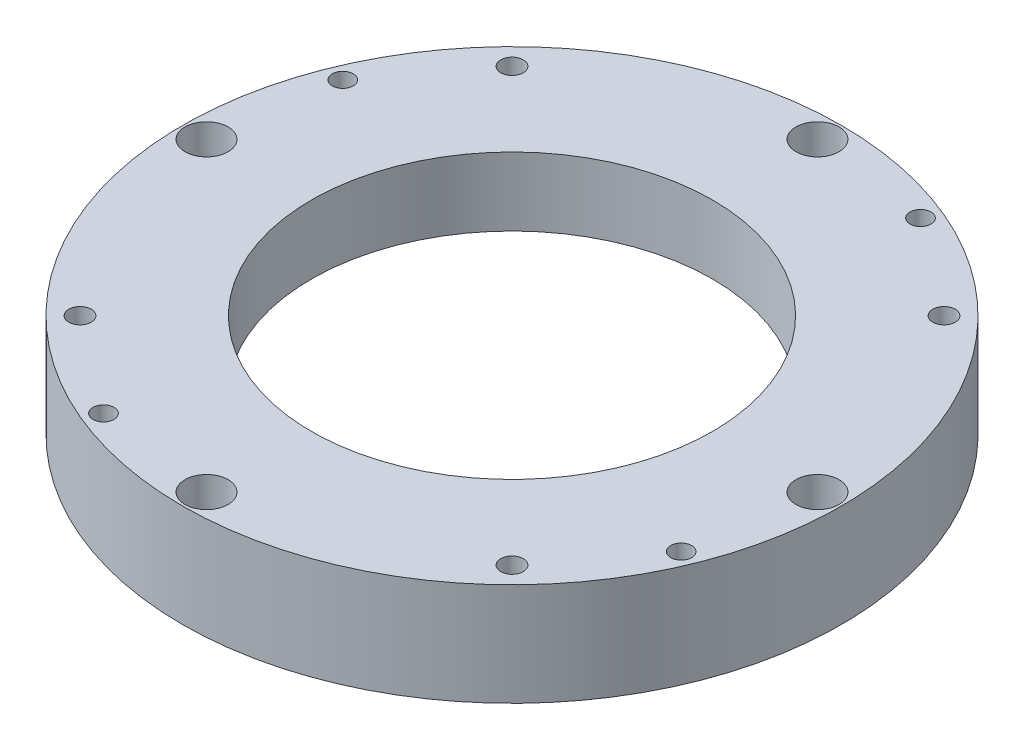
SolidWorks part; units mm, degrees
ref_plane "Front Plane" through (0, 0, 0) normal (0, 0, 1) x (1, 0, 0)
ref_plane "Top Plane" through (0, 0, 0) normal (0, 1, 0) x (1, 0, 0)
ref_plane "Right Plane" through (0, 0, 0) normal (1, 0, 0) x (0, 0, -1)
sketch "Sketch1" plane through (0, 0, 0) normal (0, 1, 0) x (1, 0, 0)
  line L0 (0, 0) -> (42.5, 0) construction
  circle A0 centre (0, 0) radius 45.85
  circle A1 centre (0, 0) radius 27.9
  circle A2 centre (42.5, 0) radius 1.5635
  circle A3 centre (30.052, -30.052) radius 1.5635
  circle A4 centre (0, -42.5) radius 1.5635
  circle A5 centre (0, 0) radius 39.5
  circle A6 centre (-30.052, -30.052) radius 1.5635
  circle A7 centre (-42.5, 0) radius 1.5635
  circle A8 centre (-30.052, 30.052) radius 1.5635
  circle A9 centre (0, 42.5) radius 1.5635
  circle A10 centre (30.052, 30.052) radius 1.5635
  point P13 (0, 0)
  dimension "D1" = 91.7
  dimension "D2" = 55.8
  dimension "D4" = 3.127
  dimension "D6" = 79
  dimension "D3" = 42.5
  dimension "D5" = 8
extrude "Boss-Extrude1" add sketch "Sketch1" against normal blind 4.7625 contours A0 A5 A2 A4 A3 region at (-44.5532, 0, 0)
extrude "Boss-Extrude2" add sketch "Sketch1<4>" along normal blind 4.7625 contours A1 A5 | A0 A5 A2 A4 A3 region at (-44.5532, 0, 0) region at (-38.3828, 0, 0)
sketch "Sketch1<4>" plane through (0, 0, 0) normal (0, 1, 0) x (1, 0, 0) same geometry as "Sketch1"
sketch "Sketch4" plane through (0, 4.7625, 0) normal (0, 1, 0) x (1, 0, 0)
  line L0 (28.4932, -27.352) -> (26.9343, -30.052)
  line L7 (30.052, 33.1697) -> (27.352, 31.6109)
  line L8 (27.352, 31.6109) -> (27.352, 28.4932)
  line L9 (27.352, 28.4932) -> (30.052, 26.9343)
  line L10 (30.052, 26.9343) -> (32.752, 28.4932)
  line L11 (32.752, 28.4932) -> (32.752, 31.6109)
  line L12 (32.752, 31.6109) -> (30.052, 33.1697)
  line L13 (31.6109, -27.352) -> (28.4932, -27.352)
  line L14 (33.1697, -30.052) -> (31.6109, -27.352)
  line L15 (31.6109, -32.752) -> (33.1697, -30.052)
  line L16 (28.4932, -32.752) -> (31.6109, -32.752)
  line L17 (26.9343, -30.052) -> (28.4932, -32.752)
  line L18 (-27.352, -28.4932) -> (-30.052, -26.9343)
  line L19 (-27.352, -31.6109) -> (-27.352, -28.4932)
  line L20 (-30.052, -33.1697) -> (-27.352, -31.6109)
  line L21 (-32.752, -31.6109) -> (-30.052, -33.1697)
  line L22 (-32.752, -28.4932) -> (-32.752, -31.6109)
  line L23 (-30.052, -26.9343) -> (-32.752, -28.4932)
  line L24 (-28.4932, 27.352) -> (-26.9343, 30.052)
  line L25 (-31.6109, 27.352) -> (-28.4932, 27.352)
  line L26 (-33.1697, 30.052) -> (-31.6109, 27.352)
  line L27 (-31.6109, 32.752) -> (-33.1697, 30.052)
  line L28 (-28.4932, 32.752) -> (-31.6109, 32.752)
  line L29 (-26.9343, 30.052) -> (-28.4932, 32.752)
  circle A0 centre (30.052, 30.052) radius 2.7 construction
  point P1 (31.402, 32.3903)
  point P32 (0, 0)
  dimension "D1" = 5.4
  dimension "D2" = 4
extrude "Cut-Extrude2" cut sketch "Sketch4" against normal blind 4.7625
sketch "Sketch3" plane through (0, 4.7625, 0) normal (0, 1, 0) x (1, 0, 0)
  circle A6 centre (0, -42.5) radius 1.5635 construction
  circle A7 centre (42.5, 0) radius 1.5635 construction
  circle A8 centre (0, 42.5) radius 1.5635 construction
  circle A9 centre (-42.5, 0) radius 1.5635 construction
  circle A10 centre (0, 0) radius 27.9 construction
  circle A11 centre (0, 0) radius 45.85 construction
  circle A12 centre (0, -42.5) radius 1.5635
  circle A13 centre (42.5, 0) radius 1.5635
  circle A14 centre (0, 42.5) radius 1.5635
  circle A15 centre (-42.5, 0) radius 1.5635
  circle A16 centre (0, 0) radius 27.9
  circle A17 centre (0, 0) radius 45.85
  circle A18 centre (0, 42.5) radius 3
  circle A19 centre (42.5, 0) radius 3
  circle A20 centre (0, -42.5) radius 3
  circle A21 centre (-42.5, 0) radius 3
  circle A22 centre (-30.052, 30.052) radius 1.565
  circle A23 centre (30.052, 30.052) radius 1.565
  circle A24 centre (30.052, -30.052) radius 1.565
  circle A25 centre (-30.052, -30.052) radius 1.565
  circle M1 centre (0, 0) radius 27.9
  circle M6 centre (0, 0) radius 45.85
  line M21 (-33.1697, 30.052) -> (-31.6109, 32.752)
  line M22 (-31.6109, 32.752) -> (-28.4932, 32.752)
  line M23 (-28.4932, 32.752) -> (-26.9343, 30.052)
  line M24 (-26.9343, 30.052) -> (-28.4932, 27.352)
  line M25 (-28.4932, 27.352) -> (-31.6109, 27.352)
  line M26 (-31.6109, 27.352) -> (-33.1697, 30.052)
  line M27 (-30.052, -33.1697) -> (-32.752, -31.6109)
  line M28 (-32.752, -31.6109) -> (-32.752, -28.4932)
  line M29 (-32.752, -28.4932) -> (-30.052, -26.9343)
  line M30 (-30.052, -26.9343) -> (-27.352, -28.4932)
  line M31 (-27.352, -28.4932) -> (-27.352, -31.6109)
  line M32 (-27.352, -31.6109) -> (-30.052, -33.1697)
  line M33 (33.1697, -30.052) -> (31.6109, -32.752)
  line M34 (31.6109, -32.752) -> (28.4932, -32.752)
  line M35 (28.4932, -32.752) -> (26.9343, -30.052)
  line M36 (26.9343, -30.052) -> (28.4932, -27.352)
  line M37 (28.4932, -27.352) -> (31.6109, -27.352)
  line M38 (31.6109, -27.352) -> (33.1697, -30.052)
  line M39 (30.052, 33.1697) -> (32.752, 31.6109)
  line M40 (32.752, 31.6109) -> (32.752, 28.4932)
  line M41 (32.752, 28.4932) -> (30.052, 26.9343)
  line M42 (30.052, 26.9343) -> (27.352, 28.4932)
  line M43 (27.352, 28.4932) -> (27.352, 31.6109)
  line M44 (27.352, 31.6109) -> (30.052, 33.1697)
  dimension "D1" = 6
  dimension "D2" = 3.13
extrude "Boss-Extrude3" add sketch "Sketch3" along normal blind 4.7625 contours A21 A20 A19 A18 M6 M1 M44 M39 M40 M41 M42 M43 M38 M33 M34 M35 M36 M37 M32 M27 M28 M29 M30 M31 M26 M21 M22 M23 M24 M25 | A22 M21 M26 M25 M24 M23 M22 | A23 M39 M44 M43 M42 M41 M40 | A24 M33 M38 M37 M36 M35 M34 | A25 M27 M32 M31 M30 M29 M28 region at (-45.7203, 4.7625, 0) region at (-32.3189, 4.7625, -31.3608) region at (-31.3608, 4.7625, 32.3189) region at (32.3189, 4.7625, 31.3608) region at (31.3608, 4.7625, -32.3189)
sketch "Sketch5" plane through (0, 9.525, 0) normal (0, 1, 0) x (1, 0, 0)
  line L0 (0, 0) -> (30.052, 30.052) construction
  circle A0 centre (0, 42.5) radius 3 construction
  circle A1 centre (30.052, 30.052) radius 1.565 construction
  circle A2 centre (42.5, 0) radius 3 construction
  circle A3 centre (30.052, -30.052) radius 1.565 construction
  circle A4 centre (0, -42.5) radius 3 construction
  circle A5 centre (-30.052, -30.052) radius 1.565 construction
  circle A6 centre (-42.5, 0) radius 3 construction
  circle A7 centre (-30.052, 30.052) radius 1.565 construction
  circle A8 centre (0, 0) radius 45.85 construction
  circle A9 centre (0, 0) radius 27.9 construction
  circle A10 centre (0, 42.5) radius 3
  circle A11 centre (30.052, 30.052) radius 1.565
  circle A12 centre (42.5, 0) radius 3
  circle A13 centre (30.052, -30.052) radius 1.565
  circle A14 centre (0, -42.5) radius 3
  circle A15 centre (-30.052, -30.052) radius 1.565
  circle A16 centre (-42.5, 0) radius 3
  circle A17 centre (-30.052, 30.052) radius 1.565
  circle A18 centre (0, 0) radius 45.85
  circle A19 centre (0, 0) radius 27.9
  arc A20 (6.31, 31.2697) -> (18.4511, 26.0224) centre (0, 0) cw
  arc A21 (4.6718, 37.2871) -> (6.4423, 39.762) centre (0, 42.5) ccw
  arc A22 (24.5734, 31.0284) -> (24.5119, 29.527) centre (30.052, 30.052) ccw
  arc A23 (24.5119, 29.527) -> (18.4511, 26.0224) centre (20.6784, 29.1636) cw
  arc A24 (4.6718, 37.2871) -> (6.31, 31.2697) centre (7, 34.6892) ccw
  arc A25 (22.8162, 35.0834) -> (24.5734, 31.0284) centre (20.6354, 31.7302) cw
  arc A26 (8.6987, 40.936) -> (6.4423, 39.762) centre (8.283, 38.9797) ccw
  arc A27 (22.8162, 35.0834) -> (8.6987, 40.936) centre (0, 0) ccw
  arc A28 (35.0834, 22.8162) -> (31.0284, 24.5734) centre (31.7302, 20.6354) ccw
  arc A29 (31.0284, 24.5734) -> (29.527, 24.5119) centre (30.052, 30.052) cw
  arc A30 (29.527, 24.5119) -> (26.0224, 18.4511) centre (29.1636, 20.6784) ccw
  arc A31 (31.2697, 6.31) -> (26.0224, 18.4511) centre (0, 0) ccw
  arc A32 (35.0834, 22.8162) -> (40.936, 8.6987) centre (0, 0) cw
  arc A33 (40.936, 8.6987) -> (39.762, 6.4423) centre (38.9797, 8.283) cw
  arc A34 (37.2871, 4.6718) -> (39.762, 6.4423) centre (42.5, 0) cw
  arc A35 (37.2871, 4.6718) -> (31.2697, 6.31) centre (34.6892, 7) cw
  arc A36 (37.2871, -4.6718) -> (31.2697, -6.31) centre (34.6892, -7) ccw
  arc A37 (31.2697, -6.31) -> (26.0224, -18.4511) centre (0, 0) cw
  arc A38 (29.527, -24.5119) -> (26.0224, -18.4511) centre (29.1636, -20.6784) cw
  arc A39 (31.0284, -24.5734) -> (29.527, -24.5119) centre (30.052, -30.052) ccw
  arc A40 (35.0834, -22.8162) -> (31.0284, -24.5734) centre (31.7302, -20.6354) cw
  arc A41 (35.0834, -22.8162) -> (40.936, -8.6987) centre (0, 0) ccw
  arc A42 (40.936, -8.6987) -> (39.762, -6.4423) centre (38.9797, -8.283) ccw
  arc A43 (37.2871, -4.6718) -> (39.762, -6.4423) centre (42.5, 0) ccw
  arc A44 (24.5119, -29.527) -> (18.4511, -26.0224) centre (20.6784, -29.1636) ccw
  arc A45 (24.5734, -31.0284) -> (24.5119, -29.527) centre (30.052, -30.052) cw
  arc A46 (22.8162, -35.0834) -> (24.5734, -31.0284) centre (20.6354, -31.7302) ccw
  arc A47 (22.8162, -35.0834) -> (8.6987, -40.936) centre (0, 0) cw
  arc A48 (6.31, -31.2697) -> (18.4511, -26.0224) centre (0, 0) ccw
  arc A49 (4.6718, -37.2871) -> (6.31, -31.2697) centre (7, -34.6892) cw
  arc A50 (4.6718, -37.2871) -> (6.4423, -39.762) centre (0, -42.5) cw
  arc A51 (8.6987, -40.936) -> (6.4423, -39.762) centre (8.283, -38.9797) cw
  arc A52 (-4.6718, -37.2871) -> (-6.31, -31.2697) centre (-7, -34.6892) ccw
  arc A53 (-6.31, -31.2697) -> (-18.4511, -26.0224) centre (0, 0) cw
  arc A54 (-24.5119, -29.527) -> (-18.4511, -26.0224) centre (-20.6784, -29.1636) cw
  arc A55 (-24.5734, -31.0284) -> (-24.5119, -29.527) centre (-30.052, -30.052) ccw
  arc A56 (-22.8162, -35.0834) -> (-24.5734, -31.0284) centre (-20.6354, -31.7302) cw
  arc A57 (-22.8162, -35.0834) -> (-8.6987, -40.936) centre (0, 0) ccw
  arc A58 (-8.6987, -40.936) -> (-6.4423, -39.762) centre (-8.283, -38.9797) ccw
  arc A59 (-4.6718, -37.2871) -> (-6.4423, -39.762) centre (0, -42.5) ccw
  arc A60 (-29.527, -24.5119) -> (-26.0224, -18.4511) centre (-29.1636, -20.6784) ccw
  arc A61 (-31.0284, -24.5734) -> (-29.527, -24.5119) centre (-30.052, -30.052) cw
  arc A62 (-35.0834, -22.8162) -> (-31.0284, -24.5734) centre (-31.7302, -20.6354) ccw
  arc A63 (-35.0834, -22.8162) -> (-40.936, -8.6987) centre (0, 0) cw
  arc A64 (-31.2697, -6.31) -> (-26.0224, -18.4511) centre (0, 0) ccw
  arc A65 (-37.2871, -4.6718) -> (-31.2697, -6.31) centre (-34.6892, -7) cw
  arc A66 (-37.2871, -4.6718) -> (-39.762, -6.4423) centre (-42.5, 0) cw
  arc A67 (-40.936, -8.6987) -> (-39.762, -6.4423) centre (-38.9797, -8.283) cw
  arc A68 (-37.2871, 4.6718) -> (-31.2697, 6.31) centre (-34.6892, 7) ccw
  arc A69 (-31.2697, 6.31) -> (-26.0224, 18.4511) centre (0, 0) cw
  arc A70 (-29.527, 24.5119) -> (-26.0224, 18.4511) centre (-29.1636, 20.6784) cw
  arc A71 (-31.0284, 24.5734) -> (-29.527, 24.5119) centre (-30.052, 30.052) ccw
  arc A72 (-35.0834, 22.8162) -> (-31.0284, 24.5734) centre (-31.7302, 20.6354) cw
  arc A73 (-35.0834, 22.8162) -> (-40.936, 8.6987) centre (0, 0) ccw
  arc A74 (-40.936, 8.6987) -> (-39.762, 6.4423) centre (-38.9797, 8.283) ccw
  arc A75 (-37.2871, 4.6718) -> (-39.762, 6.4423) centre (-42.5, 0) ccw
  arc A76 (-24.5119, 29.527) -> (-18.4511, 26.0224) centre (-20.6784, 29.1636) ccw
  arc A77 (-24.5734, 31.0284) -> (-24.5119, 29.527) centre (-30.052, 30.052) cw
  arc A78 (-22.8162, 35.0834) -> (-24.5734, 31.0284) centre (-20.6354, 31.7302) ccw
  arc A79 (-22.8162, 35.0834) -> (-8.6987, 40.936) centre (0, 0) cw
  arc A80 (-6.31, 31.2697) -> (-18.4511, 26.0224) centre (0, 0) ccw
  arc A81 (-4.6718, 37.2871) -> (-6.31, 31.2697) centre (-7, 34.6892) cw
  arc A82 (-4.6718, 37.2871) -> (-6.4423, 39.762) centre (0, 42.5) cw
  arc A83 (-8.6987, 40.936) -> (-6.4423, 39.762) centre (-8.283, 38.9797) cw
  point P137 (0, 0)
  dimension "D1" = 4
  dimension "D2" = 4
  dimension "D3" = 4
  dimension "D4" = 4
  dimension "D5" = 12
  dimension "D8" = 2
  dimension "D9" = 4
  dimension "D7" = 14
  dimension "D6" = 4
extrude "Cut-Extrude3" [suppressed] cut sketch "Sketch5" against normal blind 4.7625 contours A75 A68 A69 A70 A71 A72 A73 A74 | A83 A79 A78 A77 A76 A80 A81 A82 | A25 A27 A26 A21 A24 A20 A23 A22 | A35 A34 A33 A32 A28 A29 A30 A31 | A43 A36 A37 A38 A39 A40 A41 A42 | A51 A47 A46 A45 A44 A48 A49 A50 | A59 A52 A53 A54 A55 A56 A57 A58 | A67 A63 A62 A61 A60 A64 A65 A66
sketch "Sketch6" plane through (0, 9.525, 0) normal (0, 1, 0) x (1, 0, 0)
  line L0 (0, 0) -> (-42.5, 0) construction
  line L1 (0, 0) -> (-40.1888, 16.6467) construction
  circle A0 centre (-40.1888, 16.6467) radius 1.46
  circle A1 centre (16.6467, 40.1888) radius 1.46
  circle A2 centre (40.1888, -16.6467) radius 1.46
  circle A3 centre (-16.6467, -40.1888) radius 1.46
  point P6 (-21.3591, -41.7269)
  point P7 (0, 0)
  point P15 (0, 0)
  dimension "D1" = 2.92
  dimension "D2" = 22.5
  dimension "D3" = 43.5
  dimension "D4" = 4
extrude "Cut-Extrude4" cut sketch "Sketch6" against normal through all contours A0 | A1 | A3 | A2 region at (-40.1888, 9.525, -16.6467) region at (16.6467, 9.525, -40.1888) region at (40.1888, 9.525, 16.6467) region at (-16.6467, 9.525, 40.1888)
equation "\"bearing_21_OD\"= 21mm"
equation "\"pin_cirlce_diameter\"= 75mm"
equation "\"pin_diam\"= 6mm"
equation "\"gear_thickness\"= 4mm"
equation "\"ball_bearing_diam\"= 3.214mm"
equation "\"bearing_21_outer_clearance\"= 0.127mm'change this"
equation "\"bearing_15_OD\"= 15mm"
equation "\"bearing_15_outer_clearance\"= 0mm'change this"
equation "\"thrust_bearing_thickness\"= 5mm'measure this irl and change"
equation "\"D1@Boss-Extrude1\"=\"sheetThickness\""
equation "\"largeBearOD\"= 21mm"
equation "\"largeBearID\" = 15mm"
equation "\"largeBearOTight\"= 0.34375mm'calibrate - hold onto gears"
equation "\"largeBearITight\"= 0mm'calibrate - hold onto eccentric nut"
equation "\"largeBearFlangeDiam\" = 22.5mm"
equation "\"largeBearFlangeWidth\" = 0.8mm"
equation "\"smallBearOD\"= 14.8mm"
equation "\"smallBearOTight\"= 0mm'calibrate - hold onto bottom of gearbox"
equation "\"smallBearOLoose\"= 0mm'calibrate - able to take off topHat"
equation "\"smallBearID\" = 10mm"
equation "\"smallBearITight\" = 0mm'hold onto "
equation "\"pinCircleDiam\"= 75mm"
equation "\"pinDiam\"= 6mm"
equation "\"sheetThickness\"= 0.1875in"
equation "\"ballBearDiam\"= 3.5mm"
equation "\"thrustBearingThickness\"= 5mm'measure this irl and change"
equation "\"thrustBearingID\"= 0mm'measure this irl and change"
equation "\"thrustBearingOD\"= 0mm'measure this irl and change"
equation "\"eccentricity\" = 1mm"
equation "\"D1@Boss-Extrude2\"=\"sheetThickness\""
equation "\"D1@Boss-Extrude3\"=\"sheetThickness\""
equation "\"D1@Cut-Extrude2\"=\"sheetThickness\""
equation "\"D1@Cut-Extrude3\"=\"sheetThickness\""
